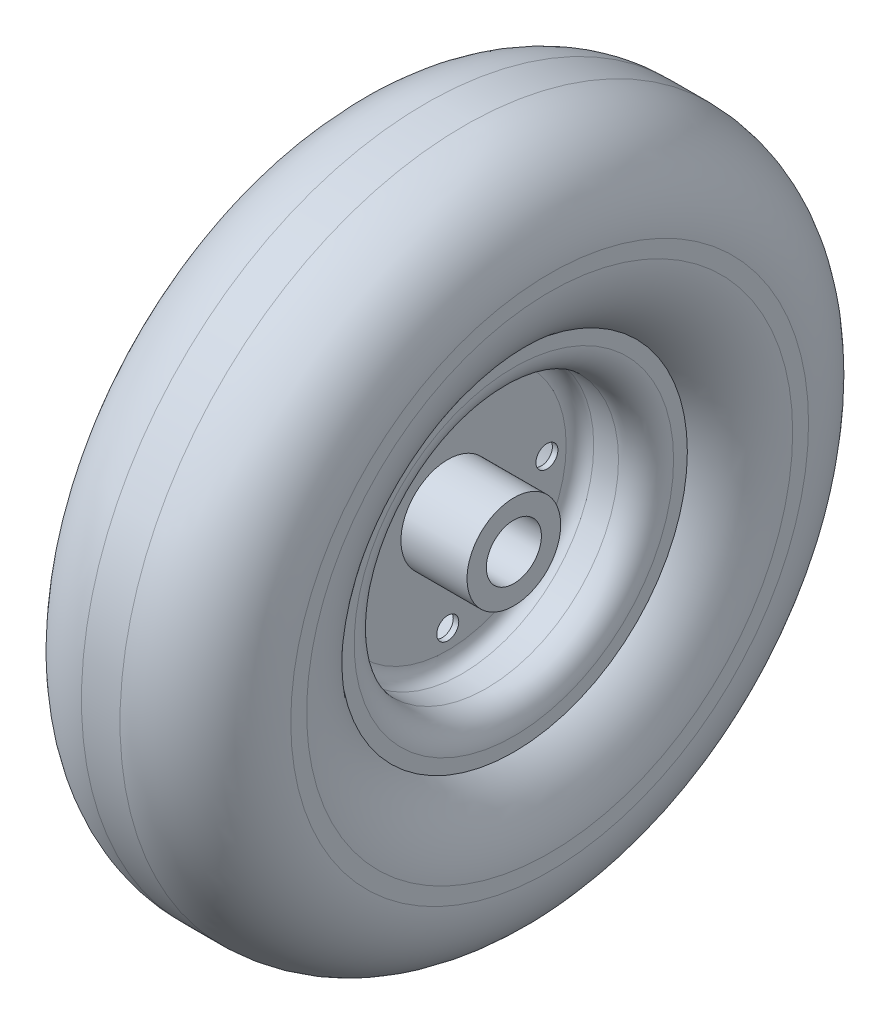
SolidWorks part; units mm, degrees
material "Rubber"
ref_plane "Front Plane" through (0, 0, 0) normal (0, 0, 1) x (1, 0, 0)
ref_plane "Top Plane" through (0, 0, 0) normal (0, 1, 0) x (1, 0, 0)
ref_plane "Right Plane" through (0, 0, 0) normal (1, 0, 0) x (0, 0, -1)
sketch "Sketch1" plane through (0, 0, 0) normal (1, 0, 0) x (0, 0, -1)
  circle A0 centre (0, 0) radius 10
  circle A1 centre (0, 0) radius 125
extrude "Boss-Extrude1" add sketch "Sketch1" along normal blind 76
sketch "Sketch2" plane through (76, 0, 0) normal (1, 0, 0) x (0, 0, -1)
  circle A0 centre (0, 0) radius 17
  circle A1 centre (0, 0) radius 48
extrude "Cut-Extrude1" cut sketch "Sketch2" against normal blind 37
sketch "Sketch3" plane through (0, 0, 0) normal (-1, 0, 0) x (0, 0, 1)
  circle A0 centre (0, 0) radius 17
  circle A1 centre (0, 0) radius 48
extrude "Cut-Extrude2" cut sketch "Sketch3" against normal blind 37
sketch "Sketch4" plane through (0, 0, 0) normal (-1, 0, 0) x (0, 0, 1)
  circle A0 centre (0, 0) radius 63
extrude "Cut-Extrude3" cut sketch "Sketch4" against normal blind 13
sketch "Sketch5" plane through (76, 0, 0) normal (1, 0, 0) x (0, 0, -1)
  circle A0 centre (0, 0) radius 63
extrude "Cut-Extrude4" cut sketch "Sketch5" against normal blind 13
sketch "Sketch6" plane through (39, 0, 0) normal (1, 0, 0) x (0, 0, -1)
  circle A0 centre (0, 36) radius 4
  circle A1 centre (0, 0) radius 17 construction
  circle A2 centre (36, 0) radius 4
  circle A3 centre (0, -36) radius 4
  circle A4 centre (-36, 0) radius 4
  point P13 (0, 0)
  dimension "D1" = 36
  dimension "D2" = 4
extrude "Cut-Extrude5" cut sketch "Sketch6" against normal through all
fillet "Fillet1" radius 31 2 edges at (76, 0, -63) (76, 0, -125)
fillet "Fillet2" radius 31 2 edges at (0, 0, 63) (0, 0, -125)
fillet "Fillet3" radius 10 2 edges at (13, 0, 48) (63, 0, -48)
fillet "Fillet4" radius 5 2 edges at (39, 0, -48) (37, 0, 48)
